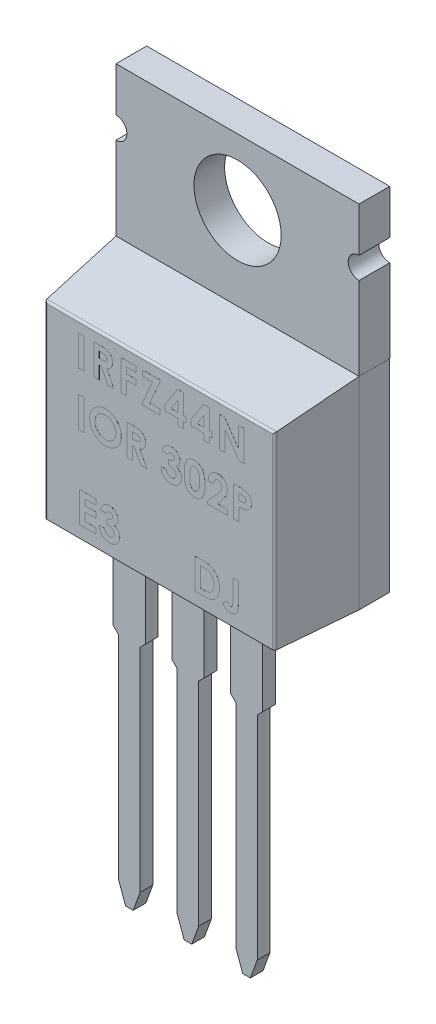
SolidWorks part; units mm, degrees
ref_plane "Front Plane" through (0, 0, 0) normal (0, 0, 1) x (1, 0, 0)
ref_plane "Top Plane" through (0, 0, 0) normal (0, 1, 0) x (1, 0, 0)
ref_plane "Right Plane" through (0, 0, 0) normal (1, 0, 0) x (0, 0, -1)
sketch "Sketch1" plane through (0, 0, 0) normal (0, 0, 1) x (1, 0, 0)
  line L1 (0, 0) -> (10.54, 0)
  line L2 (0, 0) -> (0, 15.24)
  line L3 (0, 15.24) -> (10.54, 15.24)
  line L4 (10.54, 0) -> (10.54, 15.24)
  dimension "D1" = 10.54
  dimension "D2" = 15.24
extrude "Boss-Extrude1" add sketch "Sketch1" along normal blind 1.32
sketch "Sketch3" plane through (0, 0, 1.32) normal (0, 0, 1) x (1, 0, 0)
  line L0 (10.54, 0) -> (10.54, 15.24) construction
  line L1 (0, 0) -> (10.54, 0)
  line L2 (0, 0) -> (0, 8.77)
  line L3 (0, 8.77) -> (10.54, 8.77)
  line L4 (10.54, 0) -> (10.54, 8.77)
  line L5 (10.54, 15.24) -> (0, 15.24) construction
  dimension "D1" = 6.47
extrude "Boss-Extrude2" add sketch "Sketch3" along normal blind 3.37 and the other way blind 1.32
chamfer "Chamfer1" distance 3.37 angle 10 1 edges at (5.27, 8.77, 4.69)
chamfer "Chamfer2" distance 3.37 angle 5 1 edges at (10.54, 4.0879, 4.69)
fillet "Fillet1" radius 0.1 3 edges at (10.2452, 4.0879, 4.69) (5.27, 8.1758, 4.69) (0.2948, 4.0879, 4.69)
sketch "Sketch5" plane through (0, 0, 0) normal (0, -1, 0) x (1, 0, 0)
  line L0 (5.27, 0) -> (5.27, 4.69) construction
  line L1 (4.57, 3.47) -> (5.97, 3.47)
  line L2 (4.57, 3.47) -> (4.57, 2.92)
  line L3 (4.57, 2.92) -> (5.97, 2.92)
  line L4 (5.97, 3.47) -> (5.97, 2.92)
  line L5 (0, 0) -> (10.54, 0) construction
  line L6 (0.3865, 4.69) -> (10.1535, 4.69) construction
  line L7 (7.11, 3.47) -> (8.51, 3.47)
  line L8 (7.11, 3.47) -> (7.11, 2.92)
  line L9 (7.11, 2.92) -> (8.51, 2.92)
  line L10 (8.51, 3.47) -> (8.51, 2.92)
  line L11 (4.57, 3.47) -> (5.97, 3.47)
  line L12 (4.57, 3.47) -> (4.57, 2.92)
  line L13 (4.57, 2.92) -> (5.97, 2.92)
  line L14 (5.97, 3.47) -> (5.97, 2.92)
  line L15 (2.03, 3.47) -> (3.43, 3.47)
  line L16 (2.03, 3.47) -> (2.03, 2.92)
  line L17 (2.03, 2.92) -> (3.43, 2.92)
  line L18 (3.43, 3.47) -> (3.43, 2.92)
  dimension "D1" = 1.4
  dimension "D2" = 0.55
  dimension "D3" = 0.7
  dimension "D4" = 2.92
  dimension "D5" = 2
  dimension "D6" = 2
extrude "Boss-Extrude3" add sketch "Sketch5" along normal blind 4 contours L0 L13 L4 L11 | L10 L7 L8 L9 | L15 L18 L17 L16
chamfer "Chamfer3" distance 0.235 angle 45 6 edges at (7.11, -4, 3.195) (8.51, -4, 3.195) (3.43, -4, 3.195) (2.03, -4, 3.195) (4.57, -4, 3.195) (5.97, -4, 3.195)
sketch "Sketch6" plane through (0, -4, 0) normal (0, -1, 0) x (1, 0, 0)
  line L0 (4.57, 2.92) -> (5.97, 2.92) construction
  line L1 (2.265, 3.47) -> (3.195, 3.47)
  line L2 (2.265, 3.47) -> (2.265, 2.92)
  line L3 (2.265, 2.92) -> (3.195, 2.92)
  line L4 (3.195, 3.47) -> (3.195, 2.92)
  line L5 (4.805, 3.47) -> (5.735, 3.47)
  line L6 (4.805, 3.47) -> (4.805, 2.92)
  line L7 (4.805, 2.92) -> (5.735, 2.92)
  line L8 (5.735, 3.47) -> (5.735, 2.92)
  line L9 (4.805, 2.92) -> (5.735, 2.92) construction
  line L11 (7.345, 3.47) -> (8.275, 3.47)
  line L12 (7.345, 3.47) -> (7.345, 2.92)
  line L13 (7.345, 2.92) -> (8.275, 2.92)
  line L14 (8.275, 3.47) -> (8.275, 2.92)
extrude "Boss-Extrude4" add sketch "Sketch6" along normal blind 10.03
chamfer "Chamfer4" distance 0.3 angle 70 6 edges at (2.265, -14.03, 3.195) (3.195, -14.03, 3.195) (4.805, -14.03, 3.195) (5.735, -14.03, 3.195) (7.345, -14.03, 3.195) (8.275, -14.03, 3.195)
sketch "Sketch7" plane through (0, 0, 0) normal (0, 0, -1) x (-1, 0, 0)
  line L0 (-10.54, 8.77) -> (-9.04, 8.77)
  line L1 (-10.54, 8.77) -> (0, 8.77) construction
  line L2 (-9.04, 8.77) -> (-9.04, 2)
  line L3 (-9.04, 2) -> (-1.5, 2)
  line L4 (-1.5, 2) -> (-1.5, 8.77)
  line L5 (-1.5, 8.77) -> (0, 8.77)
  line L6 (0, 0) -> (0, 15.24)
  line L7 (0, 15.24) -> (-10.54, 15.24)
  line L8 (-10.54, 15.24) -> (-10.54, 0)
  line L10 (-10.54, 0) -> (0, 0)
  line L12 (0, 0) -> (0, 15.24)
  line L13 (0, 15.24) -> (-10.54, 15.24)
  line L14 (-10.54, 15.24) -> (-10.54, 0)
  line M10 (0, 0) -> (0, 15.24)
  line M11 (0, 15.24) -> (-10.54, 15.24)
  line M14 (-10.54, 15.24) -> (-10.54, 0)
  dimension "D1" = 0
extrude "Boss-Extrude5" add sketch "Sketch7" along normal blind 0.01 and the other way blind 1.32 contours L4 L5 L0 L2 L3 M10 M11 M14
sketch "Sketch4" plane through (0, 0, 1.32) normal (0, 0, 1) x (1, 0, 0)
  line L0 (5.27, 15.24) -> (5.27, 8.77) construction
  line L1 (10.54, 15.24) -> (0, 15.24) construction
  line L2 (10.54, 8.77) -> (0, 8.77) construction
  line L3 (5.27, 12.37) -> (0, 12.37) construction
  circle A0 centre (5.27, 12.37) radius 1.89
  circle A1 centre (0, 12.8425) radius 0.4725
  circle A2 centre (10.54, 12.8425) radius 0.4725
  dimension "D1" = 2.87
  dimension "D2" = 3.78
  dimension "D3" = 0.945
extrude "Cut-Extrude1" cut sketch "Sketch4" against normal through all
sketch "Sketch8" plane through (10.54, 0, 0) normal (1, 0, 0) x (0, 0, -1)
  line L0 (-1.32, 8.77) -> (0.01, 8.77)
  line L7 (0.01, 8.77) -> (0.01, 12.37)
  line L8 (0.01, 12.37) -> (-1.32, 12.37)
  line L9 (-1.32, 12.37) -> (-1.32, 8.77)
  line L10 (-1.32, 8.77) -> (-1.32, 0)
  line L11 (-1.32, 0) -> (0, 0)
  line L12 (0, 0) -> (0, 8.77)
  line L13 (0, 8.77) -> (0.01, 8.77)
  line L14 (0.01, 8.77) -> (0.01, 12.37)
  line L15 (0.01, 12.37) -> (-1.32, 12.37)
  line L16 (-1.32, 12.37) -> (-1.32, 8.77)
  line L17 (-1.32, 8.77) -> (-1.32, 0)
  line L18 (-1.32, 0) -> (0, 0)
  line L19 (0, 0) -> (0, 8.77)
  line L20 (0, 8.77) -> (0.01, 8.77)
  line M11 (-1.32, 8.77) -> (-1.32, 0)
  line M12 (-1.32, 0) -> (0, 0)
  line M13 (0, 0) -> (0, 8.77)
  dimension "D1" = 0
extrude "Boss-Extrude6" add sketch "Sketch8" along normal blind 0.001 contours L0 M11 M12 M13
sketch "Sketch9" plane through (0, 0, 0) normal (-1, 0, 0) x (0, 0, 1)
  line L1 (1.32, 8.77) -> (0, 8.77)
  line L2 (1.32, 8.77) -> (1.32, 0)
  line L3 (1.32, 0) -> (0, 0)
  line L4 (0, 8.77) -> (0, 0)
extrude "Boss-Extrude7" add sketch "Sketch9" along normal blind 0.001
sketch "Sketch10" plane through (0, 0, 4.69) normal (0, 0, 1) x (1, 0, 0)
  text T0 "<b>IRFZ44N</b>\r\n" font "Century Gothic" height in points 5
  text T1 "<b>IOR 302P</b>" font "Century Gothic" height in points 5
  text T2 "<b>E3      DJ</b>" font "Century Gothic" height in points 5
extrude "Boss-Extrude8" add sketch "Sketch10" along normal blind 0.001
